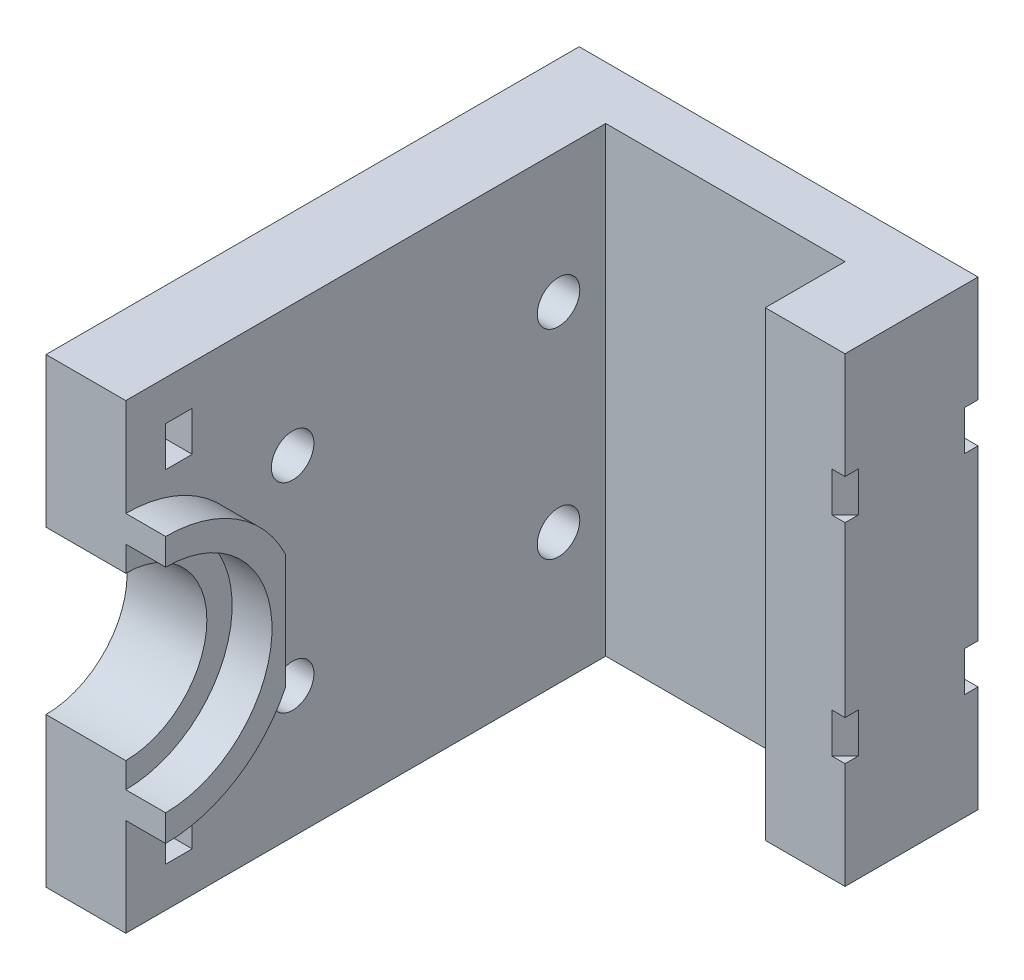
SolidWorks part; units mm, degrees
ref_plane "前基準面" through (0, 0, 0) normal (0, 0, 1) x (1, 0, 0)
ref_plane "上基準面" through (0, 0, 0) normal (0, 1, 0) x (1, 0, 0)
ref_plane "右基準面" through (0, 0, 0) normal (1, 0, 0) x (0, 0, -1)
sketch "草圖2" plane through (0, 0, 0) normal (1, 0, 0) x (0, 0, -1)
  line L1 (-13.55, 17.35) -> (13.55, 17.35)
  line L2 (-13.55, 17.35) -> (-13.55, -17.35) construction
  line L3 (-13.55, -17.35) -> (13.55, -17.35)
  line L4 (13.55, 17.35) -> (13.55, -17.35)
  line L5 (-13.55, 17.35) -> (13.55, -17.35) construction
  line L6 (-13.55, -17.35) -> (13.55, 17.35) construction
  line L7 (-10, 7.5) -> (10, 7.5) construction
  line L8 (-10, 7.5) -> (-10, -7.5) construction
  line L9 (-10, -7.5) -> (10, -7.5) construction
  line L10 (10, 7.5) -> (10, -7.5) construction
  line L11 (-10, 7.5) -> (10, -7.5) construction
  line L12 (-10, -7.5) -> (10, 7.5) construction
  line L13 (-13.55, 17.35) -> (-22.55, 17.35)
  line L14 (-13.55, 17.35) -> (-13.55, -17.35) construction
  line L15 (-13.55, -17.35) -> (-22.55, -17.35)
  line L16 (-22.55, 17.35) -> (-22.55, -17.35)
  line L17 (-19.55, -14.35) -> (-17.55, -14.35)
  line L18 (-19.55, -14.35) -> (-19.55, -11.35)
  line L19 (-19.55, -11.35) -> (-17.55, -11.35)
  line L20 (-17.55, -14.35) -> (-17.55, -11.35)
  line L21 (-19.55, 14.35) -> (-17.55, 14.35)
  line L22 (-19.55, 14.35) -> (-19.55, 11.35)
  line L23 (-19.55, 11.35) -> (-17.55, 11.35)
  line L24 (-17.55, 14.35) -> (-17.55, 11.35)
  circle A0 centre (-10, 7.5) radius 1.6
  circle A1 centre (10, 7.5) radius 1.6
  circle A2 centre (10, -7.5) radius 1.6
  circle A3 centre (-10, -7.5) radius 1.6
  arc A4 (-22.55, -6.1) -> (-22.55, 6.1) centre (-22.55, 0) ccw
  point P0 (0, 0)
  point P6 (0, 0)
  dimension "D5" = 3.2
  dimension "D6" = 3.2
  dimension "D7" = 3.2
  dimension "D8" = 3.2
  dimension "D10" = 6.1
  dimension "D1" = 27.1
  dimension "D2" = 34.7
  dimension "D3" = 20
  dimension "D4" = 15
  dimension "D9" = 9
  dimension "D11" = 2
  dimension "D12" = 3
  dimension "D13" = 3
  dimension "D14" = 3
  dimension "D15" = 3
  dimension "D16" = 3
  dimension "D17" = 3
  dimension "D18" = 2
extrude "填料-伸長1" add sketch "草圖2" along normal blind 6 contours A4 L16 L15 L3 L4 L1 L13 A3 A2 A1 A0 L20 L17 L18 L19 L21 L24 L23 L22 region at (0, 0, 3.6935)
sketch "草圖3" plane through (6, 0, 0) normal (1, 0, 0) x (0, 0, -1)
  line L0 (-22.55, -6.1) -> (-22.55, -17.35) construction
  line L1 (-22.55, 17.35) -> (-22.55, 6.1) construction
  line L2 (-13.55, 4.3589) -> (-13.55, -4.3589)
  line L4 (-22.55, 10) -> (-22.55, 8)
  line L5 (-22.55, -8) -> (-22.55, -10)
  arc A0 (-22.55, -8) -> (-22.55, 8) centre (-22.55, 0) ccw
  arc A1 (-22.55, -10) -> (-13.55, -4.3589) centre (-22.55, 0) ccw
  arc A2 (-13.55, 4.3589) -> (-22.55, 10) centre (-22.55, 0) ccw
  dimension "D1" = 8
  dimension "D2" = 10
  dimension "D3" = 9
extrude "填料-伸長2" add sketch "草圖3" along normal blind 3
sketch "草圖4" plane through (0, 0, 0) normal (-1, 0, 0) x (0, 0, 1)
  line L1 (-13.55, 17.35) -> (-17.55, 17.35)
  line L2 (-13.55, 17.35) -> (-13.55, -17.35)
  line L3 (-13.55, -17.35) -> (-17.55, -17.35)
  line L4 (-17.55, 17.35) -> (-17.55, -17.35)
  dimension "D1" = 4
extrude "填料-伸長3" add sketch "草圖4" against normal blind 24
sketch "草圖5" plane through (24, 0, 0) normal (1, 0, 0) x (0, 0, -1)
  line L0 (13.55, -17.35) -> (-22.55, -17.35) construction
  line L1 (17.55, 17.35) -> (6.55, 17.35)
  line L2 (17.55, 17.35) -> (17.55, -17.35)
  line L3 (17.55, -17.35) -> (6.55, -17.35)
  line L4 (6.55, 17.35) -> (6.55, -17.35)
  dimension "D1" = 11
ref_plane "平面1" through (0, -9.35, 0) normal (0, -1, 0) x (-1, 0, 0)
ref_plane "平面2" through (0, 9.35, 0) normal (0, 1, 0) x (1, 0, 0)
sketch "草圖10" plane through (0, 0, 0) normal (-1, 0, 0) x (0, 0, 1)
  line L1 (-17.55, 17.35) -> (-21.55, 17.35)
  line L2 (-17.55, 17.35) -> (-17.55, -17.35)
  line L3 (-17.55, -17.35) -> (-21.55, -17.35)
  line L4 (-21.55, 17.35) -> (-21.55, -17.35)
  dimension "D1" = 4
sketch "草圖15" plane through (24, 0, 0) normal (1, 0, 0) x (0, 0, -1)
  line L0 (17.55, -17.35) -> (6.55, -17.35) construction
  line L1 (17.55, 17.35) -> (7.55, 17.35)
  line L2 (17.55, 17.35) -> (17.55, -17.35)
  line L3 (17.55, -17.35) -> (7.55, -17.35)
  line L4 (7.55, 17.35) -> (7.55, -17.35)
  dimension "D1" = 10
extrude "填料-伸長8" add sketch "草圖15" along normal blind 6
sketch "草圖16" plane through (0, 0, -17.55) normal (0, 0, -1) x (-1, 0, 0)
  line L0 (-24, 17.35) -> (-24, -17.35) construction
  line L1 (-24, 9.35) -> (-22, 9.35)
  line L2 (-24, 9.35) -> (-24, 6.35)
  line L3 (-24, 6.35) -> (-22, 6.35)
  line L4 (-22, 9.35) -> (-22, 6.35)
  line L5 (16.5, 9.35) -> (-16.5, 9.35) construction
  line L6 (-16.5, -9.35) -> (16.5, -9.35) construction
  line L7 (-24, -9.35) -> (-22, -9.35)
  line L8 (-24, -9.35) -> (-24, -6.35)
  line L9 (-24, -6.35) -> (-22, -6.35)
  line L10 (-22, -9.35) -> (-22, -6.35)
  dimension "D1" = 2
  dimension "D2" = 3
  dimension "D3" = 2
  dimension "D4" = 3
extrude "除料-伸長4" cut sketch "草圖16" against normal blind 6
sketch "草圖17" plane through (0, -9.35, 0) normal (0, -1, 0) x (-1, 0, 0)
  line L0 (-30, 17.55) -> (-29, 17.55)
  line L1 (-30, 17.55) -> (0, 17.55) construction
  line L2 (-29, 17.55) -> (-30, 16.55)
  line L3 (-30, 7.55) -> (-30, 17.55) construction
  line L4 (-30, 16.55) -> (-30, 17.55)
  line L5 (-30, 7.55) -> (-30, 8.55)
  line L6 (-30, 8.55) -> (-29, 7.55)
  line L7 (-30, 7.55) -> (-24, 7.55) construction
  line L8 (-29, 7.55) -> (-30, 7.55)
  dimension "D1" = 1
  dimension "D2" = 1
  dimension "D3" = 1
  dimension "D4" = 1
extrude "除料-伸長5" cut sketch "草圖17" against normal blind 3
sketch "草圖18" plane through (0, 9.35, 0) normal (0, 1, 0) x (1, 0, 0)
  line L0 (30, 17.55) -> (29, 17.55)
  line L1 (30, 17.55) -> (0, 17.55) construction
  line L2 (29, 17.55) -> (30, 16.55)
  line L3 (30, 16.55) -> (30, 17.55)
  line L4 (30, 7.55) -> (30, 8.55)
  line L5 (30, 17.55) -> (30, 7.55) construction
  line L6 (30, 8.55) -> (29, 7.55)
  line L7 (30, 7.55) -> (24, 7.55) construction
  line L8 (29, 7.55) -> (30, 7.55)
  dimension "D1" = 1
  dimension "D2" = 1
  dimension "D3" = 1
  dimension "D4" = 1
extrude "除料-伸長6" cut sketch "草圖18" against normal blind 3
